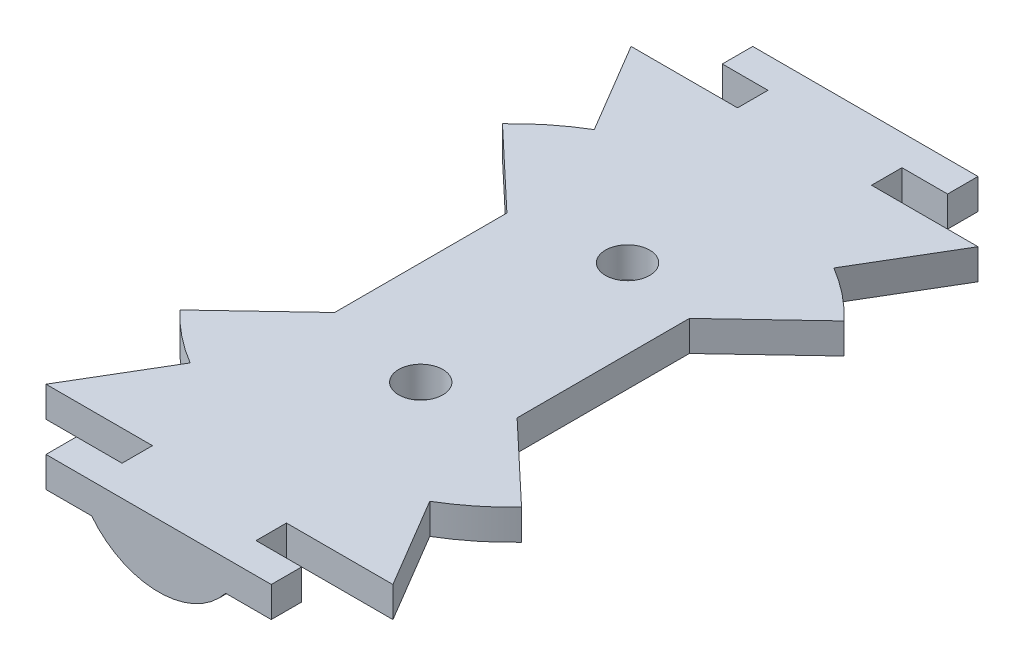
SolidWorks part; units mm, degrees
ref_plane "Front Plane" through (0, 0, 0) normal (0, 0, 1) x (1, 0, 0)
ref_plane "Top Plane" through (0, 0, 0) normal (0, 1, 0) x (1, 0, 0)
ref_plane "Right Plane" through (0, 0, 0) normal (1, 0, 0) x (0, 0, -1)
ref_plane "Plane1" through (0, -1.4717, 0) normal (0, -1, 0) x (-1, 0, 0)
sketch "Sketch1" plane through (0, -1.4717, 0) normal (0, -1, 0) x (-1, 0, 0)
  line L0 (8.1511, 13.3541) -> (11.5781, 19.1336) construction
  line L1 (8.1511, 13.3541) -> (11.5781, 19.1336)
  line L2 (7.8777, 13.2851) -> (11.4061, 19.2356)
  line L3 (0, 0) -> (0, 50000) construction
  line L4 (0, 0) -> (50000, 0) construction
  line L6 (11.4061, 19.2356) -> (4.4061, 19.2356)
  line L7 (11.2303, 10.6035) -> (6, 5.6651)
  line L8 (4.4061, 19.2356) -> (4.4061, 21.2356)
  line L9 (4.4061, 21.2356) -> (7.4061, 21.2356)
  line L10 (7.4061, 21.2356) -> (7.4061, 23.2356)
  line L11 (7.4061, 23.2356) -> (-7.4061, 23.2356)
  line L12 (-7.4061, 21.2356) -> (-7.4061, 23.2356)
  line L13 (-4.4061, 21.2356) -> (-7.4061, 21.2356)
  line L14 (-4.4061, 19.2356) -> (-4.4061, 21.2356)
  line L15 (-11.4061, 19.2356) -> (-4.4061, 19.2356)
  line L16 (-7.8777, 13.2851) -> (-11.4061, 19.2356)
  line L19 (-7.8777, -13.2851) -> (-11.4061, -19.2356)
  line L20 (-11.4061, -19.2356) -> (-4.4061, -19.2356)
  line L21 (-4.4061, -19.2356) -> (-4.4061, -21.2356)
  line L22 (-4.4061, -21.2356) -> (-7.4061, -21.2356)
  line L23 (-7.4061, -21.2356) -> (-7.4061, -23.2356)
  line L24 (7.4061, -23.2356) -> (-7.4061, -23.2356)
  line L25 (7.4061, -21.2356) -> (7.4061, -23.2356)
  line L26 (4.4061, -21.2356) -> (7.4061, -21.2356)
  line L27 (4.4061, -19.2356) -> (4.4061, -21.2356)
  line L28 (11.4061, -19.2356) -> (4.4061, -19.2356)
  line L30 (7.8777, -13.2851) -> (11.4061, -19.2356)
  line L31 (6, 5.6651) -> (6, -5.6651)
  line L32 (-11.2303, 10.6035) -> (-6, 5.6651)
  line L33 (-6, 5.6651) -> (-6, -5.6651)
  line L34 (11.2303, -10.6035) -> (6, -5.6651)
  line L35 (-11.2303, -10.6035) -> (-6, -5.6651)
  line L36 (8, 7.7) -> (8, -7.7) construction
  arc A0 (10.6568, 11.4544) -> (8.1511, 13.3541) centre (0, 0) ccw construction
  arc A1 (10.6568, 11.4544) -> (8.1511, 13.3541) centre (0, 0) ccw
  arc A2 (10.5206, 11.308) -> (7.8777, 13.2851) centre (0, 0) ccw
  arc A3 (10.5206, 11.308) -> (11.2303, 10.6035) centre (0, 0) cw
  arc A4 (-10.5206, 11.308) -> (-7.8777, 13.2851) centre (0, 0) cw
  arc A5 (-10.5206, 11.308) -> (-11.2303, 10.6035) centre (0, 0) ccw
  arc A6 (-10.5206, -11.308) -> (-11.2303, -10.6035) centre (0, 0) cw
  arc A7 (-10.5206, -11.308) -> (-7.8777, -13.2851) centre (0, 0) ccw
  arc A8 (10.5206, -11.308) -> (11.2303, -10.6035) centre (0, 0) ccw
  arc A9 (10.5206, -11.308) -> (7.8777, -13.2851) centre (0, 0) cw
  point P21 (0, 23.2356)
  point P35 (0, -23.2356)
  point P49 (6, 0)
  point P50 (-6, 0)
  dimension "D2" = 7
  dimension "D3" = 2
  dimension "D4" = 2
  dimension "D5" = 3
  dimension "D6" = 2
  dimension "D7" = 1
  dimension "D1" = 0.2
extrude "Boss-Extrude1" add sketch "Sketch1" along normal blind 2 contours A9 A8 A3 A2 L2 L6 L8 L9 L10 L11 L12 L13 L14 L15 L16 A4 A5 A6 A7 L19 L20 L21 L22 L23 L24 L25 L26 L27 L28 L30 region at (0, -1.4717, 0)
sketch "Sketch2" plane through (0, 0, -23.2356) normal (0, 0, -1) x (-1, 0, 0)
  line L0 (-4.4061, -3.4717) -> (4.4061, -3.4717)
  line L1 (7.4061, -3.4717) -> (-7.4061, -3.4717) construction
  line L2 (7.4061, -3.4717) -> (7.4061, -1.4717) construction
  arc A0 (-4.4061, -3.4717) -> (4.4061, -3.4717) centre (0, 0) ccw
  point P5 (0, -3.4717)
  line M4 (-7.4061, -3.4717) -> (7.4061, -3.4717)
  dimension "D1" = 3
extrude "Boss-Extrude2" add sketch "Sketch2" against normal blind 7 contours A0 M4 region at (0, -4.3425, -23.2356)
pattern_circular "CirPattern1" count 2 every 180 of "Boss-Extrude2"
fillet "Fillet2" radius 2.2 2 edges at (0, -3.4717, -16.2356) (0, -3.4717, 16.2356)
sketch "Sketch3" plane through (0, -1.4717, 0) normal (0, -1, 0) x (-1, 0, 0)
  line L6 (-3.5, 8.5) -> (-3.5, -8.5)
  line L7 (-2.5, -9.5) -> (8.75, -9.5)
  line L8 (10.75, -7.5) -> (14.5, -7.5)
  line L9 (15.5, -6.5) -> (15.5, 6.5)
  line L10 (14.5, 7.5) -> (10.75, 7.5)
  line L11 (8.75, 9.5) -> (-2.5, 9.5)
  line L12 (-3.5, 8.5) -> (-3.5, -8.5)
  line L13 (-2.5, -9.5) -> (8.75, -9.5)
  line L14 (10.75, -7.5) -> (14.5, -7.5)
  line L15 (15.5, -6.5) -> (15.5, 6.5)
  line L16 (14.5, 7.5) -> (10.75, 7.5)
  line L17 (8.75, 9.5) -> (-2.5, 9.5)
  circle A0 centre (-0.8, 6.8) radius 1.45 construction
  circle A1 centre (-0.8, -6.8) radius 1.45 construction
  circle A2 centre (-0.8, 6.8) radius 1.45
  circle A3 centre (-0.8, -6.8) radius 1.45
  arc A8 (-3.5, -8.5) -> (-2.5, -9.5) centre (-2.5, -8.5) ccw
  arc A9 (8.75, -9.5) -> (9.75, -8.5) centre (8.75, -8.5) ccw
  arc A10 (10.75, -7.5) -> (9.75, -8.5) centre (10.75, -8.5) ccw
  arc A11 (14.5, -7.5) -> (15.5, -6.5) centre (14.5, -6.5) ccw
  arc A12 (15.5, 6.5) -> (14.5, 7.5) centre (14.5, 6.5) ccw
  arc A13 (9.75, 8.5) -> (10.75, 7.5) centre (10.75, 8.5) ccw
  arc A14 (9.75, 8.5) -> (8.75, 9.5) centre (8.75, 8.5) ccw
  arc A15 (-2.5, 9.5) -> (-3.5, 8.5) centre (-2.5, 8.5) ccw
  arc A16 (-3.5, -8.5) -> (-2.5, -9.5) centre (-2.5, -8.5) ccw
  arc A17 (8.75, -9.5) -> (9.75, -8.5) centre (8.75, -8.5) ccw
  arc A18 (10.75, -7.5) -> (9.75, -8.5) centre (10.75, -8.5) ccw
  arc A19 (14.5, -7.5) -> (15.5, -6.5) centre (14.5, -6.5) ccw
  arc A20 (15.5, 6.5) -> (14.5, 7.5) centre (14.5, 6.5) ccw
  arc A21 (9.75, 8.5) -> (10.75, 7.5) centre (10.75, 8.5) ccw
  arc A22 (9.75, 8.5) -> (8.75, 9.5) centre (8.75, 8.5) ccw
  arc A23 (-2.5, 9.5) -> (-3.5, 8.5) centre (-2.5, 8.5) ccw
  dimension "D1" = 0
hole_wizard "M2.5 Clearance Hole1" positions "Sketch4" profile "Sketch5" hole size "M2.5" standard "ANSI Metric" end condition through all
sketch "Sketch4" plane through (0, -3.4717, 0) normal (0, -1, 0) x (-1, 0, 0)
  point P0 (-0.8, 6.8)
  point P3 (-0.8, -6.8)
sketch "Sketch5" plane through (0.8, -3.4717, -6.8) normal (1, 0, 0) x (0, 0, -1)
  line L0 (0, 0) -> (0, 2)
  line L1 (0, 2) -> (1.45, 2)
  line L2 (1.45, 2) -> (1.45, 0)
  line L5 (1.45, 0) -> (0, 0)
  line L11 (0, -6.35) -> (0, 107.95) construction
  dimension "Thru Hole Dia." = 2.9
  dimension "Thru Hole Depth" = 2
